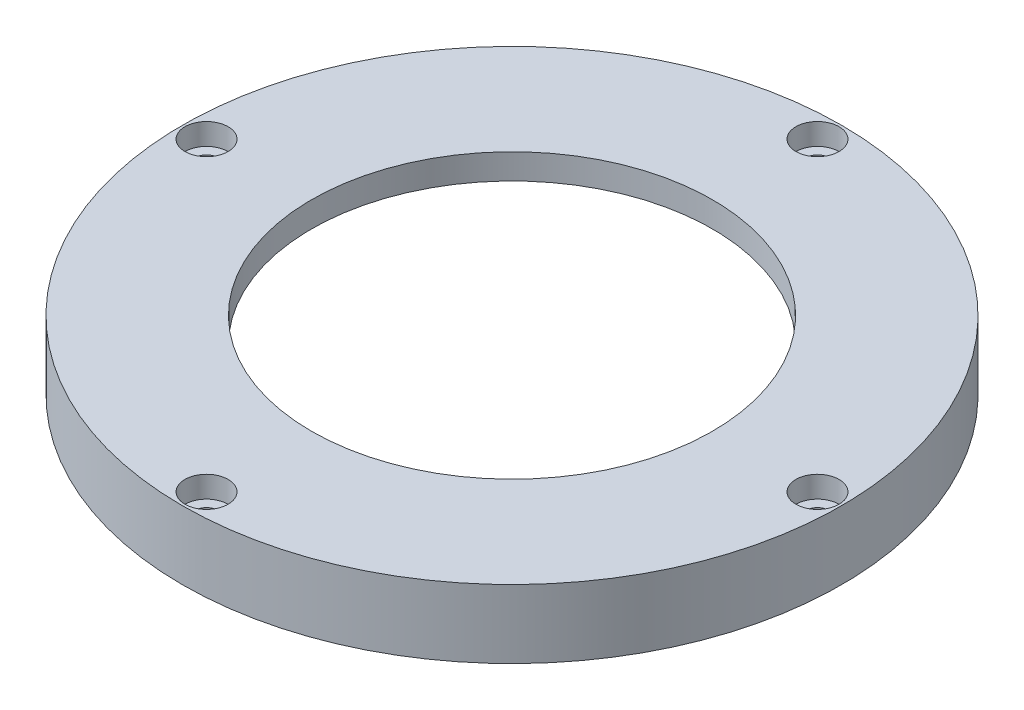
SolidWorks part; units mm, degrees
ref_plane "Front Plane" through (0, 0, 0) normal (0, 0, 1) x (1, 0, 0)
ref_plane "Top Plane" through (0, 0, 0) normal (0, 1, 0) x (1, 0, 0)
ref_plane "Right Plane" through (0, 0, 0) normal (1, 0, 0) x (0, 0, -1)
sketch "Sketch1" plane through (0, 0, 0) normal (0, 1, 0) x (1, 0, 0)
  line L0 (0, 0) -> (42.5, 0) construction
  circle A0 centre (0, 0) radius 45.85
  circle A1 centre (0, 0) radius 27.9
  circle A2 centre (42.5, 0) radius 1.5635
  circle A3 centre (0, -42.5) radius 1.5635
  circle A4 centre (-42.5, 0) radius 1.5635
  circle A5 centre (0, 0) radius 39.3
  circle A6 centre (0, 42.5) radius 1.5635
  point P13 (0, 0)
  dimension "D1" = 91.7
  dimension "D2" = 55.8
  dimension "D4" = 3.127
  dimension "D6" = 78.6
  dimension "D3" = 42.5
  dimension "D5" = 4
extrude "Boss-Extrude1" add sketch "Sketch1" against normal blind 6 contours A0 A5 A2 A4 A3 region at (-44.5532, 0, 0)
extrude "Boss-Extrude2" add sketch "Sketch1<4>" along normal blind 3.525 contours A1 A5 | A0 A5 A2 A4 A3 region at (-44.5532, 0, 0) region at (-38.1884, 0, 0)
sketch "Sketch1<4>" plane through (0, 0, 0) normal (0, 1, 0) x (1, 0, 0) same geometry as "Sketch1"
sketch "Sketch2" plane through (0, 3.525, 0) normal (0, 1, 0) x (1, 0, 0)
  circle A0 centre (42.5, 0) radius 3
  circle A1 centre (0, -42.5) radius 3
  circle A2 centre (-42.5, 0) radius 3
  circle A3 centre (0, 42.5) radius 3
  point P3 (0, 0)
  point P4 (-65.4034, -13.2807)
  point P9 (0, 0)
  point P17 (0, 0)
  dimension "D1" = 6
  dimension "D2" = 4
extrude "Cut-Extrude1" cut sketch "Sketch2" against normal blind 3
equation "\"bearing_21_OD\"= 21mm"
equation "\"pin_cirlce_diameter\"= 75mm"
equation "\"pin_diam\"= 6mm"
equation "\"gear_thickness\"= 4mm"
equation "\"ball_bearing_diam\"= 3.214mm"
equation "\"bearing_21_outer_clearance\"= 0.127mm'change this"
equation "\"bearing_15_OD\"= 15mm"
equation "\"bearing_15_outer_clearance\"= 0mm'change this"
equation "\"thrust_bearing_thickness\"= 5mm'measure this irl and change"
equation "\"D1@Boss-Extrude1\"=\"thrustBearingThickness\"+1mm"
equation "\"largeBearOD\"= 21mm"
equation "\"largeBearID\"= 15mm"
equation "\"largeBearOTight\"= 0.127mm'calibrate - hold onto gears"
equation "\"largeBearITight\"= 0mm'calibrate - hold onto eccentric nut"
equation "\"largeBearFlangeDiam\"= 22.5mm"
equation "\"largeBearFlangeWidth\"= 0.8mm"
equation "\"smallBearOD\"= 15mm"
equation "\"smallBearOTight\"= 0mm'calibrate - hold onto bottom of gearbox"
equation "\"smallBearOLoose\"= 0mm'calibrate - able to take off topHat"
equation "\"smallBearID\"= 10mm"
equation "\"smallBearITight\"= 0mm'hold onto "
equation "\"pinCircleDiam\"= 75mm"
equation "\"pinDiam\"= 6mm"
equation "\"sheetThickness\"= 0.1875in"
equation "\"ballBearDiam\"= 3.214mm"
equation "\"thrustBearingThickness\"= 5mm'measure this irl and change"
equation "\"thrustBearingID\"= 0mm'measure this irl and change"
equation "\"thrustBearingOD\"= 0mm'measure this irl and change"
equation "\"eccentricity\"= 1mm"
equation "\"D1@Boss-Extrude2\"=\"sheetThickness\"*2-(\"thrustBearingThickness\"+1)"
